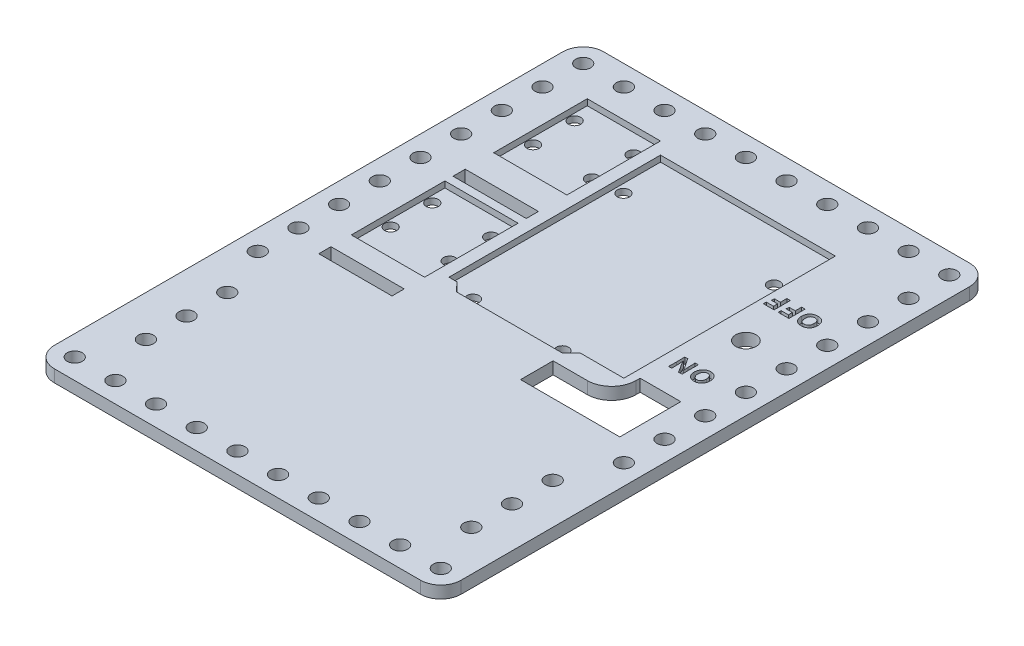
SolidWorks part; units mm, degrees
material "Copper"
ref_plane "Front Plane" through (0, 0, 0) normal (0, 0, 1) x (1, 0, 0)
ref_plane "Top Plane" through (0, 0, 0) normal (0, 1, 0) x (1, 0, 0)
ref_plane "Right Plane" through (0, 0, 0) normal (1, 0, 0) x (0, 0, -1)
sketch "Sketch1" plane through (0, 0, 0) normal (0, 1, 0) x (1, 0, 0)
  line L1 (6.35, 0) -> (120.65, 0)
  line L2 (0, 6.35) -> (0, 165.1)
  line L3 (6.35, 171.45) -> (120.65, 171.45)
  line L4 (127, 6.35) -> (127, 165.1)
  arc A0 (6.35, 0) -> (0, 6.35) centre (6.35, 6.35) cw
  arc A1 (120.65, 0) -> (127, 6.35) centre (120.65, 6.35) ccw
  arc A2 (120.65, 171.45) -> (127, 165.1) centre (120.65, 165.1) cw
  arc A3 (0, 165.1) -> (6.35, 171.45) centre (6.35, 165.1) cw
  point P7 (0, 0)
  point P10 (127, 0)
  point P13 (127, 171.45)
  point P16 (0, 171.45)
  dimension "D3" = 6.35
  dimension "D1" = 127
  dimension "D2" = 171.45
extrude "Plate Extrude" add sketch "Sketch1" along normal blind 3.81
sketch "Sketch2" plane through (0, 3.81, 0) normal (0, 1, 0) x (1, 0, 0)
  line L0 (120.65, 171.45) -> (6.35, 171.45) construction
  line L1 (0, 165.1) -> (0, 6.35) construction
  line L2 (6.35, 0) -> (120.65, 0) construction
  line L3 (63.5, 171.45) -> (63.5, 0) construction
  circle A0 centre (6.35, 165.1) radius 2.3495
  circle A1 centre (19.05, 165.1) radius 2.3495
  circle A2 centre (31.75, 165.1) radius 2.3495
  circle A3 centre (44.45, 165.1) radius 2.3495
  circle A4 centre (57.15, 165.1) radius 2.3495
  circle A5 centre (69.85, 165.1) radius 2.3495
  circle A6 centre (82.55, 165.1) radius 2.3495
  circle A7 centre (95.25, 165.1) radius 2.3495
  circle A8 centre (107.95, 165.1) radius 2.3495
  circle A9 centre (120.65, 165.1) radius 2.3495
  circle A10 centre (6.35, 152.4) radius 2.3495
  circle A11 centre (120.65, 152.4) radius 2.3495
  circle A12 centre (6.35, 139.7) radius 2.3495
  circle A13 centre (120.65, 139.7) radius 2.3495
  circle A14 centre (6.35, 127) radius 2.3495
  circle A15 centre (120.65, 127) radius 2.3495
  circle A16 centre (6.35, 114.3) radius 2.3495
  circle A17 centre (120.65, 114.3) radius 2.3495
  circle A18 centre (6.35, 101.6) radius 2.3495
  circle A19 centre (120.65, 101.6) radius 2.3495
  circle A20 centre (6.35, 88.9) radius 2.3495
  circle A21 centre (120.65, 88.9) radius 2.3495
  circle A22 centre (6.35, 76.2) radius 2.3495
  circle A23 centre (120.65, 76.2) radius 2.3495
  circle A24 centre (6.35, 63.5) radius 2.3495
  circle A25 centre (120.65, 63.5) radius 2.3495
  circle A26 centre (6.35, 6.35) radius 2.3495
  circle A27 centre (19.05, 6.35) radius 2.3495
  circle A28 centre (31.75, 6.35) radius 2.3495
  circle A29 centre (44.45, 6.35) radius 2.3495
  circle A30 centre (57.15, 6.35) radius 2.3495
  circle A31 centre (69.85, 6.35) radius 2.3495
  circle A32 centre (82.55, 6.35) radius 2.3495
  circle A33 centre (95.25, 6.35) radius 2.3495
  circle A34 centre (107.95, 6.35) radius 2.3495
  circle A35 centre (120.65, 6.35) radius 2.3495
  circle A36 centre (12.7, 22.225) radius 2.3495
  circle A37 centre (12.7, 34.925) radius 2.3495
  circle A38 centre (12.7, 47.625) radius 2.3495
  circle A39 centre (114.3, 47.625) radius 2.3495
  circle A40 centre (114.3, 34.925) radius 2.3495
  circle A41 centre (114.3, 22.225) radius 2.3495
  dimension "D1" = 4.699
  dimension "D2" = 6.35
  dimension "D6" = 4.699
  dimension "D7" = 6.35
  dimension "D8" = 6.35
  dimension "D10" = 4.699
  dimension "D11" = 12.7
  dimension "D12" = 22.225
  dimension "D3" = 6.35
  dimension "D4" = 10
  dimension "D5" = 9
  dimension "D9" = 10
  dimension "D13" = 3
extrude "Outer Hole Cut" cut sketch "Sketch2" against normal through all
sketch "Sketch3" plane through (0, 3.81, 0) normal (0, 1, 0) x (1, 0, 0)
  line L0 (81.28, 83.566) -> (84.074, 86.36)
  line L1 (43.18, 152.4) -> (97.79, 152.4)
  line L2 (43.18, 152.4) -> (43.18, 86.36)
  line L3 (43.18, 86.36) -> (97.79, 86.36)
  line L4 (97.79, 152.4) -> (97.79, 86.36)
  line L5 (81.28, 83.566) -> (48.26, 83.566)
  line L6 (48.26, 83.566) -> (45.72, 86.36)
  line L7 (127, 6.35) -> (127, 165.1) construction
  line L8 (120.65, 171.45) -> (6.35, 171.45) construction
  circle A0 centre (78.867, 86.106) radius 1.905
  circle A1 centre (50.927, 86.106) radius 1.905
  circle A2 centre (94.107, 136.906) radius 1.905
  circle A3 centre (45.847, 138.176) radius 1.905
  dimension "D1" = 3.81
  dimension "D9" = 52.07
  dimension "D2" = 54.61
  dimension "D3" = 66.04
  dimension "D4" = 40.894
  dimension "D5" = 38.1
  dimension "D6" = 5.08
  dimension "D7" = 27.94
  dimension "D8" = 7.747
  dimension "D10" = 50.8
  dimension "D11" = 15.24
  dimension "D12" = 5.08
  dimension "D13" = 2.54
  dimension "D14" = 2.794
  dimension "D15" = 2.54
  dimension "D16" = 29.21
  dimension "D17" = 19.05
extrude "Arduino Shape Cut" cut sketch "Sketch3" against normal blind 1.905 contours A1 L3 A0 L4 L1 L2 A3 A2 | A1 L3 L6 L5 L0 A0 region at (64.8255, 3.81, -84.9307) region at (70.503, 3.81, -119.3498)
sketch "Sketch4" plane through (0, 3.81, 0) normal (0, 1, 0) x (1, 0, 0)
  line L0 (43.18, 152.4) -> (43.18, 86.36) construction
  line L1 (16.51, 127) -> (39.37, 127)
  line L2 (16.51, 127) -> (16.51, 156.21)
  line L3 (16.51, 156.21) -> (39.37, 156.21)
  line L4 (39.37, 127) -> (39.37, 156.21)
  line L5 (43.18, 152.4) -> (97.79, 152.4) construction
  line L6 (16.51, 82.55) -> (39.37, 82.55)
  line L7 (16.51, 82.55) -> (16.51, 111.76)
  line L8 (39.37, 82.55) -> (39.37, 111.76)
  line L9 (16.51, 111.76) -> (39.37, 111.76)
  circle A0 centre (18.6057, 137.1834) radius 1.905
  circle A1 centre (18.6057, 150.1829) radius 1.905
  circle A2 centre (37.005, 150.1829) radius 1.905
  circle A3 centre (37.005, 137.1834) radius 1.905
  circle A4 centre (18.6057, 92.7334) radius 1.905
  circle A5 centre (18.6057, 105.7329) radius 1.905
  circle A6 centre (37.005, 105.7329) radius 1.905
  circle A7 centre (37.005, 92.7334) radius 1.905
  dimension "D1" = 3.81
  dimension "D9" = 18.3993
  dimension "D2" = 22.86
  dimension "D3" = 29.21
  dimension "D4" = 10.1834
  dimension "D5" = 2.365
  dimension "D6" = 3.81
  dimension "D7" = 12.9995
  dimension "D8" = 3.81
  dimension "D10" = 2
extrude "HG7881 Shape Cut" cut sketch "Sketch4" against normal blind 1.905 contours L1 L4 L3 L2 A3 A2 A1 A0 | L9 L7 L6 L8 A7 A6 A5 A4 region at (27.9499, 3.81, -141.4527) region at (27.9499, 3.81, -97.0027)
sketch "Sketch5" plane through (0, 3.81, 0) normal (0, 1, 0) x (1, 0, 0)
  circle A0 centre (94.107, 136.906) radius 1.905 construction
  circle A1 centre (78.867, 86.106) radius 1.905 construction
  circle A2 centre (50.927, 86.106) radius 1.905 construction
  circle A3 centre (45.847, 138.176) radius 1.905 construction
  circle A4 centre (18.6057, 150.1829) radius 1.905 construction
  circle A5 centre (37.005, 150.1829) radius 1.905 construction
  circle A6 centre (37.005, 137.1834) radius 1.905 construction
  circle A7 centre (18.6057, 137.1834) radius 1.905 construction
  circle A8 centre (18.6057, 105.7329) radius 1.905 construction
  circle A9 centre (18.6057, 92.7334) radius 1.905 construction
  circle A10 centre (37.005, 92.7334) radius 1.905 construction
  circle A11 centre (37.005, 105.7329) radius 1.905 construction
  circle A12 centre (94.107, 136.906) radius 1.905
  circle A13 centre (78.867, 86.106) radius 1.905
  circle A14 centre (50.927, 86.106) radius 1.905
  circle A15 centre (45.847, 138.176) radius 1.905
  circle A16 centre (18.6057, 150.1829) radius 1.905
  circle A17 centre (37.005, 150.1829) radius 1.905
  circle A18 centre (37.005, 137.1834) radius 1.905
  circle A19 centre (18.6057, 137.1834) radius 1.905
  circle A20 centre (18.6057, 105.7329) radius 1.905
  circle A21 centre (18.6057, 92.7334) radius 1.905
  circle A22 centre (37.005, 92.7334) radius 1.905
  circle A23 centre (37.005, 105.7329) radius 1.905
extrude "Arduino and HG7881 Hole Cut" cut sketch "Sketch5" against normal through all
sketch "Sketch6" plane through (0, 3.81, 0) normal (0, 1, 0) x (1, 0, 0)
  line L0 (97.79, 133.35) -> (115.57, 133.35) construction
  line L1 (97.79, 152.4) -> (97.79, 86.36) construction
  line L2 (120.65, 171.45) -> (6.35, 171.45) construction
  line L3 (106.68, 101.6) -> (106.68, 133.35) construction
  line L4 (97.79, 101.6) -> (115.57, 101.6) construction
  circle A0 centre (106.68, 115.57) radius 3.175
  text T0 "OFF" font "Dubai" height 5.08
  text T1 "ON" font "Candara" height 5.08
  dimension "D4" = 6.35
  dimension "D1" = 17.78
  dimension "D2" = 31.75
  dimension "D3" = 38.1
  dimension "D5" = 13.97
extrude "On-Off Text Cut" cut sketch "Sketch6" against normal blind 1.905
sketch "Sketch8" plane through (0, 1.905, 0) normal (0, 1, 0) x (1, 0, 0)
  circle A0 centre (106.68, 115.57) radius 3.175 construction
  circle A1 centre (106.68, 115.57) radius 3.175
extrude "Switch Hole Cut" cut sketch "Sketch8" against normal through all
sketch "Sketch9" plane through (0, 3.81, 0) normal (0, 1, 0) x (1, 0, 0)
  line L0 (113.03, 69.85) -> (82.0443, 69.85)
  line L1 (82.0443, 69.85) -> (82.0443, 80.01)
  line L2 (113.03, 69.85) -> (113.03, 88.9)
  line L3 (113.03, 88.9) -> (100.33, 88.9)
  line L4 (100.33, 88.9) -> (100.33, 87.63)
  line L5 (92.71, 80.01) -> (82.0443, 80.01)
  line L6 (97.79, 152.4) -> (97.79, 86.36) construction
  line L7 (84.074, 86.36) -> (97.79, 86.36) construction
  arc A0 (100.33, 87.63) -> (92.71, 80.01) centre (92.71, 87.63) cw
  dimension "D7" = 7.62
  dimension "D1" = 12.7
  dimension "D2" = 2.54
  dimension "D3" = 19.05
  dimension "D4" = 10.16
  dimension "D5" = 30.9857
  dimension "D6" = 2.54
extrude "Battery Wire Cut" cut sketch "Sketch9" against normal through all
sketch "Sketch10" plane through (0, 3.81, 0) normal (0, 1, 0) x (1, 0, 0)
  line L0 (16.51, 82.55) -> (16.51, 111.76) construction
  line L1 (39.37, 114.3) -> (16.51, 114.3)
  line L2 (39.37, 114.3) -> (39.37, 118.11)
  line L3 (39.37, 118.11) -> (16.51, 118.11)
  line L4 (16.51, 114.3) -> (16.51, 118.11)
  line L5 (39.37, 82.55) -> (39.37, 111.76) construction
  line L6 (16.51, 127) -> (39.37, 127) construction
  line L7 (39.37, 72.39) -> (16.51, 72.39)
  line L8 (39.37, 72.39) -> (39.37, 76.2)
  line L9 (39.37, 76.2) -> (16.51, 76.2)
  line L10 (16.51, 72.39) -> (16.51, 76.2)
  line L11 (16.51, 82.55) -> (39.37, 82.55) construction
  dimension "D1" = 3.81
  dimension "D2" = 12.7
  dimension "D3" = 3.81
  dimension "D4" = 10.16
extrude "Motor Wire Cut" cut sketch "Sketch10" against normal through all
